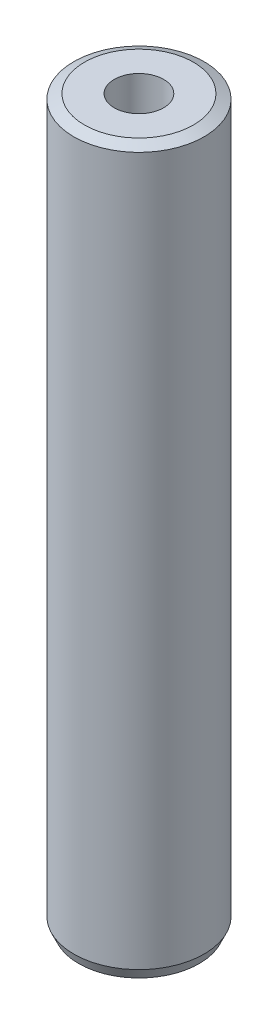
SolidWorks part; units mm, degrees
ref_plane "Front Plane" through (0, 0, 0) normal (0, 0, 1) x (1, 0, 0)
ref_plane "Top Plane" through (0, 0, 0) normal (0, 1, 0) x (1, 0, 0)
ref_plane "Right Plane" through (0, 0, 0) normal (1, 0, 0) x (0, 0, -1)
sketch "Sketch1" plane through (0, 0, 0) normal (0, 1, 0) x (1, 0, 0)
  circle A0 centre (0, 0) radius 37.5
  dimension "SHAFT_OD" = 75
extrude "Boss-Extrude1" add sketch "Sketch1" along normal blind 416.345
sketch "Sketch2" plane through (0, 0, 0) normal (0, 1, 0) x (1, 0, 0)
  circle A0 centre (0, 0) radius 14.1995
  dimension "BORE_D" = 28.3991
extrude "Cut-Extrude1" cut sketch "Sketch2" along normal through all
chamfer "Chamfer1" distance 2.7934 angle 65.58 2 edges at (0, 416.345, 37.5) (0, 0, 37.5) first distance on face at (0, 416.345, 37.5) first distance on face at (0, 0, 14.1995)
